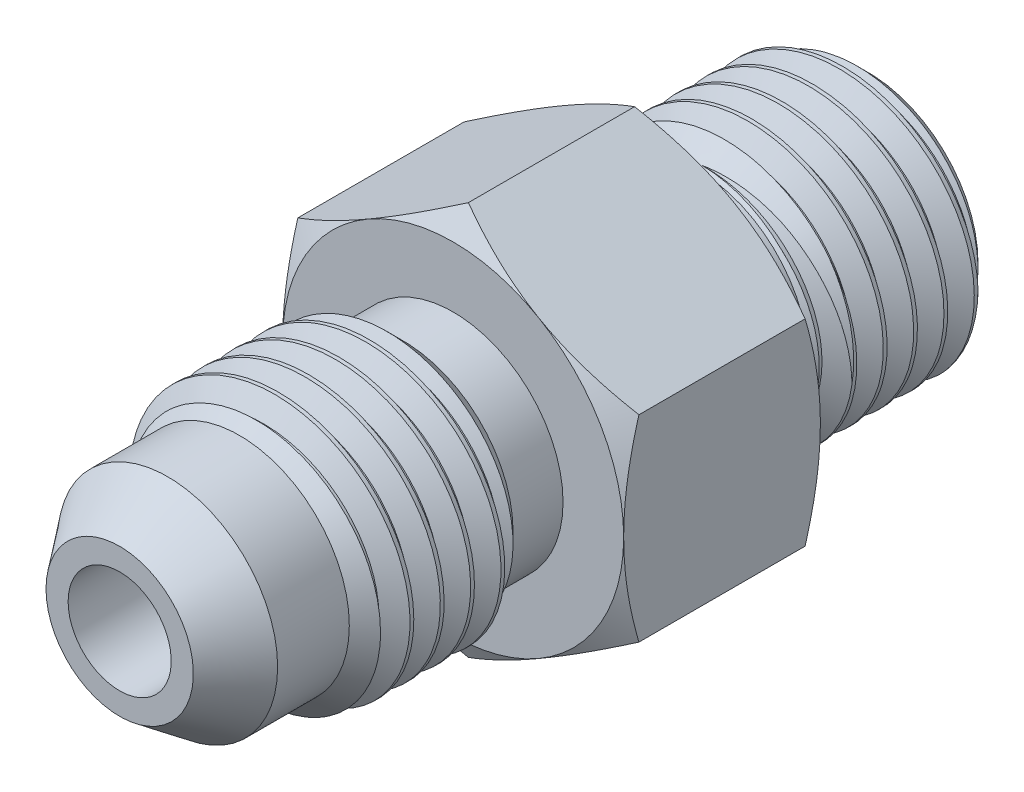
SolidWorks part; units mm, degrees
other "O-Ring" parameters "D8"=0.9525, "D1"=15.3309, "Thread Length 2"=7.112, "D2"=35.3119, "Thread Diameter 2"=6.35, "Minimum ID 2"=7.62, "Thread Pitch 2"=1.27, "Side Length 2"=9.144, "Length"=31.3538, "Side Length 1"=13.97, "Thread Length 1"=6.858, "Thread Diameter 1"=5.5562, "D3"=1.5238, "Thread 1 Offset"=0.9525, "Thread 2 Offset"=0.9525, "Thread Pitch 1"=1.27, "D4"=12.8, "Side Length Offset"=11.8745, "D5"=5.0165, "D6"=11.1125, "D7"=0.9525, "Side Length 1 Offset"=11.8745, "Face Diameter 1"=6.1722
ref_plane "Front Plane" through (0, 0, 0) normal (0, 0, 1) x (1, 0, 0)
ref_plane "Top Plane" through (0, 0, 0) normal (0, 1, 0) x (1, 0, 0)
ref_plane "Right Plane" through (0, 0, 0) normal (1, 0, 0) x (0, 0, -1)
sketch "Sketch1" plane through (0, 0, 0) normal (0, 0, 1) x (1, 0, 0)
  line L0 (0, -24.1967) -> (0, 24.1967) construction
  line L1 (0, 8.2489) -> (-7.1437, 4.1244) construction
  line L2 (-7.1437, 4.1244) -> (-7.1438, -4.1244) construction
  line L3 (-7.1438, -4.1244) -> (0, -8.2489) construction
  line L4 (0, -8.2489) -> (7.1438, -4.1244) construction
  line L5 (7.1438, -4.1244) -> (7.1438, 4.1244) construction
  line L6 (7.1438, 4.1244) -> (0, 8.2489) construction
  circle A0 centre (0, 0) radius 7.1438 construction
  circle A1 centre (0, 0) radius 2.159 construction
  point P1 (-2.159, 0)
  point P10 (-7.1437, 4.1244)
  point P11 (7.1438, 4.1244)
  point P13 (2.159, 0)
  point P14 (0, 2.159)
  point P15 (0, -2.159)
  point P16 (0, -7.1438)
  point P19 (-7.1438, -4.1244)
  point P20 (0, 8.2489)
  point P21 (0, -8.2489)
  point P22 (7.1438, -4.1244)
  point P23 (0, 7.1438)
  point P24 (7.1437, 0)
  point P25 (-7.1438, 0)
  dimension "Hex" = 14.2875
  dimension "Minimum ID 1" = 4.318
sketch "Sketch2" plane through (0, 0, 0) normal (1, 0, 0) x (0, 0, -1)
  line L0 (15.6766, 0) -> (-15.6766, 0) construction
  line L1 (8.5646, 4.6037) -> (9.5171, 5.5562) construction
  line L2 (20.955, 0) -> (-20.955, 0) construction
  line L11 (-1.7066, 7.1438) -> (6.5326, 7.1438) construction
  line L12 (6.5326, 7.1438) -> (6.5326, 4.6037) construction
  line L13 (6.5326, 4.6037) -> (8.5646, 4.6037) construction
  line L21 (-15.6766, 2.159) -> (-15.6766, 4.6037) construction
  line L22 (8.5646, 4.6037) -> (8.5646, 5.5562) construction
  line L23 (8.5646, 5.5562) -> (15.6766, 5.5562) construction
  line L24 (15.6766, 4.6037) -> (14.7241, 5.5562) construction
  line L25 (15.6766, 5.5562) -> (15.6766, 2.159) construction
  line L27 (-10.6601, 4.6037) -> (-10.6601, 5.5562) construction
  line L28 (-10.6601, 5.5562) -> (-3.8021, 5.5562) construction
  line L29 (-3.8021, 5.5562) -> (-3.8021, 4.6037) construction
  line L30 (-3.8021, 4.6037) -> (-1.7066, 4.6037) construction
  line L31 (-1.7066, 4.6037) -> (-1.7066, 7.1438) construction
  line L32 (-10.6601, -5.5562) -> (-3.8021, -5.5562) construction
  line L33 (15.6766, -5.5563) -> (8.5646, -5.5562) construction
  line L34 (15.5972, 5.6937) -> (16.8672, 5.6937) construction
  line L35 (16.8672, 5.6937) -> (16.2322, 4.5939) construction
  line L36 (16.2322, 4.5939) -> (15.5972, 5.6937) construction
  line L37 (15.6369, 5.625) -> (16.8275, 5.625) construction
  line L38 (15.6766, 5.5562) -> (16.7878, 5.5562) construction
  line L39 (16.1528, 4.7314) -> (16.3116, 4.7314) construction
  line L40 (16.2322, 4.7314) -> (16.2322, 4.5939) construction
  line L41 (16.2322, 5.6937) -> (16.2322, 5.5562) construction
  line L42 (-11.8507, 5.6937) -> (-10.5807, 5.6937) construction
  line L43 (-10.5807, 5.6937) -> (-11.2157, 4.5939) construction
  line L44 (-11.2157, 4.5939) -> (-11.8507, 5.6937) construction
  line L45 (-11.811, 5.625) -> (-10.6204, 5.625) construction
  line L46 (-11.7713, 5.5562) -> (-10.6601, 5.5562) construction
  line L47 (-11.2951, 4.7314) -> (-11.1363, 4.7314) construction
  line L48 (-11.2157, 4.7314) -> (-11.2157, 4.5939) construction
  line L49 (-11.2157, 5.5562) -> (-11.2157, 5.6937) construction
  line L53 (-15.6766, 3.0861) -> (-13.6626, 4.6037) construction
  line L54 (-1.7066, 4.6037) -> (2.413, 4.6037) construction
  line L55 (6.5326, 4.6037) -> (2.413, 4.6037) construction
  line L58 (-15.6766, 2.159) -> (-1.7066, 2.159) construction
  line L59 (-1.7066, 2.159) -> (6.5326, 2.159) construction
  line L60 (6.5326, 2.159) -> (15.6766, 2.159) construction
  line L61 (2.413, 2.159) -> (2.413, 7.1438) construction
  line L63 (-10.6601, 4.6037) -> (-9.7076, 5.5562) construction
  line L64 (-15.6766, 4.6037) -> (-10.6601, 4.6037) construction
  line L65 (-3.8021, 4.6037) -> (-4.7546, 5.5562) construction
  circle A0 centre (7.0088, 5.08) radius 0.4763 construction
  point P4 (0, 0)
  point P10 (15.6766, 4.6037)
  point P11 (-15.6766, 2.159)
  point P16 (-10.6601, 5.5562)
  point P21 (-15.6766, 4.6037)
  point P22 (-3.8021, 5.5562)
  point P24 (15.6766, -5.5563)
  point P25 (-10.6601, 5.5562)
  point P26 (8.5646, 4.6037)
  point P28 (15.6766, 0)
  point P29 (13.7716, -5.5563)
  point P31 (-1.7066, 7.1438)
  point P34 (15.6766, 5.5562)
  point P35 (-15.6766, 0)
  point P38 (15.6766, 2.159)
  point P52 (16.2322, 5.625)
  point P53 (16.3116, 4.7314)
  point P54 (16.7878, 5.5562)
  point P55 (16.1528, 4.7314)
  point P56 (16.8672, 5.6937)
  point P57 (15.6766, 5.5562)
  point P58 (15.5972, 5.6937)
  point P59 (-8.7551, -5.5562)
  point P66 (6.5326, 7.1438)
  point P71 (-11.7713, 5.5562)
  point P72 (-11.8507, 5.6937)
  point P73 (-10.6601, 5.5562)
  point P74 (-10.5807, 5.6937)
  point P75 (-11.2951, 4.7314)
  point P76 (-11.1363, 4.7314)
  point P79 (-11.2157, 5.625)
  point P82 (-15.6766, 3.0861)
  point P83 (-10.6601, -5.5562)
  point P84 (-13.6626, 4.6037)
  dimension "D2" = 0.1588
  dimension "Length" = 31.3531
  dimension "D1" = 1.905
  dimension "Thread 2 Offset" = 0.9525
  dimension "D3" = 0.1588
  dimension "D4" = 1.905
  dimension "Thread Diameter 1" = 11.1125
  dimension "Thread Diameter 2" = 11.1125
  dimension "D6" = 45
  dimension "D7" = 45
  dimension "Minimum ID 2" = 4.318
  dimension "D5" = 37
ref_plane "Plane1" through (0, 0, 10.6601) normal (0, 0, 1) x (1, 0, 0)
ref_plane "Plane2" through (0, 0, -15.6766) normal (0, 0, 1) x (1, 0, 0)
ref_plane "Plane3" through (0, 0, 1.7066) normal (0, 0, 1) x (1, 0, 0)
sketch "Sketch3" plane through (0, 0, 0) normal (1, 0, 0) x (0, 0, -1)
  line L0 (15.6766, 0) -> (-15.6766, 0) construction
  line L1 (-15.6766, 2.159) -> (-15.6766, 4.6037) construction
  line L2 (-15.6766, 2.159) -> (-1.7066, 2.159) construction
  line L3 (-1.7066, 2.159) -> (6.5326, 2.159) construction
  line L4 (6.5326, 2.159) -> (15.6766, 2.159) construction
  line L5 (15.6766, 5.5562) -> (15.6766, 2.159) construction
  line L6 (15.6766, 4.6037) -> (14.7241, 5.5562) construction
  line L7 (8.5646, 5.5562) -> (15.6766, 5.5562) construction
  line L8 (8.5646, 4.6037) -> (9.5171, 5.5562) construction
  line L10 (-3.8021, 4.6037) -> (-1.7066, 4.6037)
  line L12 (-15.6766, 4.6037) -> (-10.6601, 4.6037) construction
  line L14 (8.5646, 4.6037) -> (6.5326, 4.6037)
  line L15 (-10.6601, 5.5562) -> (-3.8021, 5.5562) construction
  line L16 (-10.6601, 4.6037) -> (-9.7076, 5.5562) construction
  line L17 (-15.6766, 3.0861) -> (-13.6626, 4.6037) construction
  line L18 (-15.6766, 3.0861) -> (-13.6626, 4.6037)
  line L19 (15.6766, 0) -> (-15.6766, 0) construction
  line L20 (-15.6766, 2.159) -> (-15.6766, 3.0861)
  line L21 (-15.6766, 2.159) -> (-1.7066, 2.159)
  line L22 (-1.7066, 2.159) -> (6.5326, 2.159)
  line L23 (6.5326, 2.159) -> (15.6766, 2.159)
  line L24 (15.6766, 4.6037) -> (15.6766, 2.159)
  line L25 (15.6766, 4.6037) -> (14.7241, 5.5562)
  line L26 (9.5171, 5.5562) -> (14.7241, 5.5562)
  line L27 (8.5646, 4.6037) -> (9.5171, 5.5562)
  line L34 (-9.7076, 5.5562) -> (-4.7546, 5.5562)
  line L35 (-10.6601, 4.6037) -> (-9.7076, 5.5562)
  line L36 (-13.6626, 4.6037) -> (-10.6601, 4.6037)
  line L37 (-3.8021, 4.6037) -> (-4.7546, 5.5562) construction
  line L41 (-1.7066, 4.6037) -> (6.5326, 4.6037)
  line L46 (-3.8021, 4.6037) -> (-4.7546, 5.5562)
revolve "Revolve1" add sketch "Sketch3" angle 360 about L19
sketch "Sketch4" plane through (0, 0, 1.7066) normal (0, 0, 1) x (1, 0, 0)
  line L0 (-7.1437, 4.1244) -> (-7.1438, -4.1244) construction
  line L1 (-7.1438, -4.1244) -> (0, -8.2489) construction
  line L2 (0, -8.2489) -> (7.1438, -4.1244) construction
  line L3 (7.1438, -4.1244) -> (7.1438, 4.1244) construction
  line L4 (7.1438, 4.1244) -> (0, 8.2489) construction
  line L5 (0, 8.2489) -> (-7.1437, 4.1244) construction
  line L6 (-7.1437, 4.1244) -> (-7.1438, -4.1244)
  line L7 (-7.1438, -4.1244) -> (0, -8.2489)
  line L8 (0, -8.2489) -> (7.1438, -4.1244)
  line L9 (7.1438, -4.1244) -> (7.1438, 4.1244)
  line L10 (7.1438, 4.1244) -> (0, 8.2489)
  line L11 (0, 8.2489) -> (-7.1437, 4.1244)
extrude "Boss-Extrude1" add sketch "Sketch4" against normal up to vertex (8.2391 mm away) up to point (0, 7.1438, -6.5326)
sketch "Sketch5" plane through (0, 0, 0) normal (1, 0, 0) x (0, 0, -1)
  line L0 (15.6766, 0) -> (-15.6766, 0) construction
  line L1 (6.5326, 2.159) -> (15.6766, 2.159) construction
  line L2 (-1.7066, 2.159) -> (6.5326, 2.159) construction
  line L3 (-15.6766, 2.159) -> (-1.7066, 2.159) construction
  line L4 (15.6766, 0) -> (-15.6766, 0)
  line L5 (6.5326, 2.159) -> (15.6766, 2.159)
  line L6 (-1.7066, 2.159) -> (6.5326, 2.159)
  line L7 (-15.6766, 2.159) -> (-1.7066, 2.159)
  line L8 (-15.6766, 2.159) -> (-15.6766, 0)
  line L9 (15.6766, 2.159) -> (15.6766, 0)
revolve "Cut-Revolve1" cut sketch "Sketch5" angle 360 about L4
sketch "Sketch6" plane through (0, 0, 1.7066) normal (0, 0, 1) x (1, 0, 0)
  circle A0 centre (0, 0) radius 7.1438 construction
  circle A1 centre (0, 0) radius 7.1438
extrude "Cut-Extrude1" cut sketch "Sketch6" against normal through all draft 60 flip side to cut
sketch "Sketch7" plane through (0, 0, -6.5326) normal (0, 0, -1) x (-1, 0, 0)
  circle A0 centre (0, 0) radius 7.1438 construction
  circle A1 centre (0, 0) radius 7.1438
extrude "Cut-Extrude2" cut sketch "Sketch7" against normal through all draft 60 flip side to cut
sketch "Sketch8" plane through (0, 0, 0) normal (1, 0, 0) x (0, 0, -1)
  circle A0 centre (7.0088, 5.08) radius 0.4763 construction
  circle A1 centre (7.0088, 5.08) radius 0.4763
revolve "Revolve2" add sketch "Sketch8" angle 360 about L0
sketch "Sketch9" plane through (0, 0, 10.6601) normal (0, 0, 1) x (1, 0, 0)
  circle A4 centre (0, 0) radius 5.5562
curve "Helix/Spiral1" pitch 1.27 height 8.128 turns 6.4
sketch "Sketch10" plane through (0, 0, 0) normal (1, 0, 0) x (0, 0, -1)
  line L0 (-11.2951, 4.7314) -> (-11.1363, 4.7314) construction
  line L1 (-11.811, 5.625) -> (-10.6204, 5.625) construction
  line L2 (-11.2951, 4.7314) -> (-11.1363, 4.7314)
  line L3 (-11.811, 5.625) -> (-10.6204, 5.625)
  line L4 (-10.5807, 5.6937) -> (-11.2157, 4.5939) construction
  line L5 (-11.2157, 4.5939) -> (-11.8507, 5.6937) construction
  line L6 (-10.6204, 5.625) -> (-11.1363, 4.7314)
  line L7 (-11.2951, 4.7314) -> (-11.811, 5.625)
sweep "Cut-Sweep1" cut profiles "Sketch10" path "Helix/Spiral1" align with end faces yes
sketch "Sketch11" plane through (0, 0, -15.6766) normal (0, 0, 1) x (1, 0, 0)
  circle A0 centre (0, 0) radius 5.5562
curve "Helix/Spiral2" pitch 1.27 height 8.382 turns 6.6
sketch "Sketch12" plane through (0, 0, 0) normal (1, 0, 0) x (0, 0, -1)
  line L0 (16.2322, 4.5939) -> (15.5972, 5.6937) construction
  line L1 (16.8672, 5.6937) -> (16.2322, 4.5939) construction
  line L2 (16.1528, 4.7314) -> (16.3116, 4.7314) construction
  line L3 (15.6369, 5.625) -> (16.8275, 5.625) construction
  line L4 (16.1528, 4.7314) -> (15.6369, 5.625)
  line L5 (16.8275, 5.625) -> (16.3116, 4.7314)
  line L6 (16.1528, 4.7314) -> (16.3116, 4.7314)
  line L7 (15.6369, 5.625) -> (16.8275, 5.625)
sweep "Cut-Sweep2" cut profiles "Sketch12" path "Helix/Spiral2" align with end faces yes
sketch "Sketch13" plane through (0, 0, -6.5326) normal (0, 0, -1) x (-1, 0, 0)
  circle A0 centre (0, 0) radius 7.1438 construction
  circle A1 centre (0, 0) radius 7.1438
  circle A2 centre (0, 0) radius 2.159
  point P3 (0, 2.159)
extrude "Boss-Extrude2" add sketch "Sketch13" against normal up to vertex (8.2391 mm away) up to point (0, 7.1438, 1.7066)
equation "\"D2@Sketch2\"=\"Thread Pitch 2@Sketch2\"/8"
equation "\"D1@Sketch2\"=\"Thread Pitch 2@Sketch2\"*1.5"
equation "\"D3@Sketch2\"=\"Thread Pitch 1@Sketch2\"/8"
equation "\"D4@Sketch2\"=\"Thread Pitch 1@Sketch2\"*1.5"
equation "\"D3@Helix/Spiral1\"=\"Thread Length 1@Sketch2\"+\"Thread Pitch 1@Sketch2\""
equation "\"D4@Helix/Spiral1\"=\"Thread Pitch 1@Sketch2\""
equation "\"D3@Helix/Spiral2\"=\"Thread Length 2@Sketch2\"+\"Thread Pitch 2@Sketch2\""
equation "\"D4@Helix/Spiral2\"=\"Thread Pitch 2@Sketch2\""
